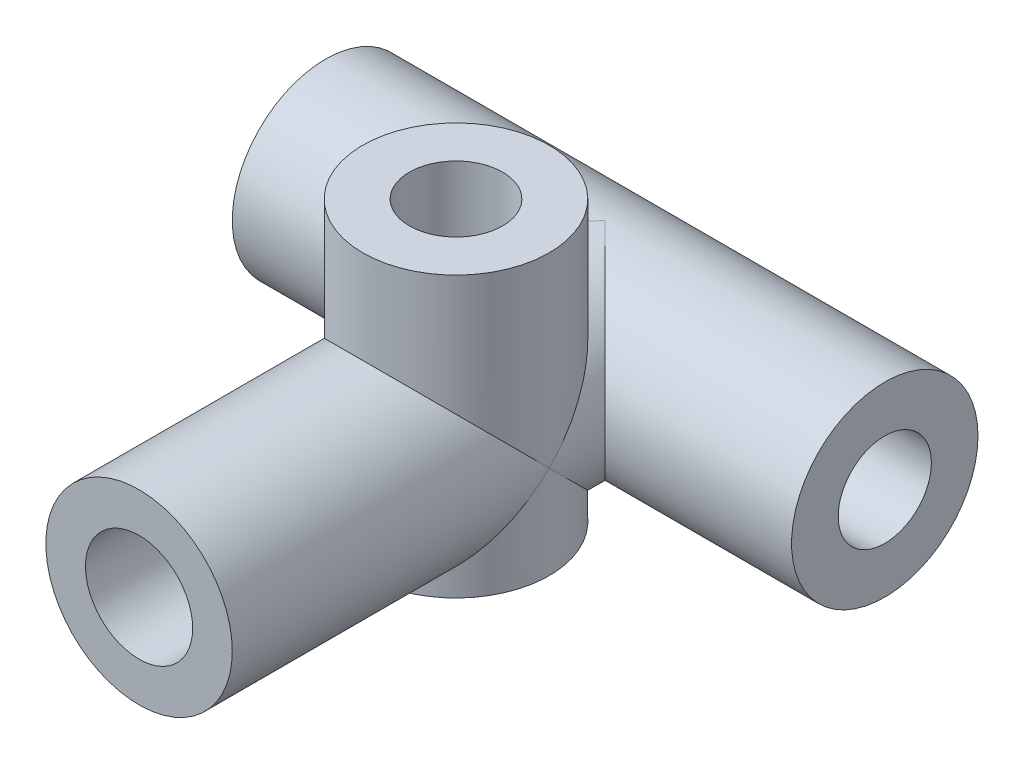
SolidWorks part; units mm, degrees
ref_plane "Plan de face" through (0, 0, 0) normal (0, 0, 1) x (1, 0, 0)
ref_plane "Plan de dessus" through (0, 0, 0) normal (0, 1, 0) x (1, 0, 0)
ref_plane "Plan de droite" through (0, 0, 0) normal (1, 0, 0) x (0, 0, -1)
sketch "Esquisse1" plane through (0, 0, 0) normal (1, 0, 0) x (0, 0, -1)
  circle A0 centre (0, 0) radius 2
  dimension "D1" = 4
extrude "Boss.-Extru.1" add sketch "Esquisse1" against normal blind 12
sketch "Esquisse5" plane through (0, 0, 0) normal (0, 0, 1) x (1, 0, 0)
  line L0 (-6, 2) -> (-6, -2) construction
  line L1 (0, 2) -> (-12, 2) construction
  line L2 (-12, -2) -> (0, -2) construction
  circle A0 centre (-6, 0) radius 2
extrude "Boss.-Extru.4" add sketch "Esquisse5" along normal blind 10 contours A0
sketch "Esquisse2" plane through (0, 0, 0) normal (1, 0, 0) x (0, 0, -1)
  circle A0 centre (0, 0) radius 1
  dimension "D1" = 2
extrude "Enlèv. mat.-Extru.1" cut sketch "Esquisse2" against normal through all
sketch "Esquisse7" plane through (0, 0, 0) normal (0, 1, 0) x (1, 0, 0)
  line L0 (-8, -3.2) -> (-4, -3.2) construction
  line L1 (-8, -2) -> (-8, -10) construction
  line L2 (-4, -10) -> (-4, -2) construction
  line L5 (-12, -2) -> (-8, -2) construction
  circle A0 centre (-6, -3.2) radius 2
  dimension "D2" = 4
  dimension "D1" = 1.2
extrude "Boss.-Extru.5" add sketch "Esquisse7" along normal blind 4 and the other way blind 2 contours A0
sketch "Esquisse8" plane through (0, 0, 10) normal (0, 0, 1) x (1, 0, 0)
  line L0 (-8, 0) -> (-4, 0) construction
  arc A0 (-6, 2) -> (-6, -2) centre (-6, 0) ccw construction
  circle A1 centre (-6, 0) radius 2 construction
  circle A2 centre (-6, 0) radius 1.15
  dimension "D1" = 2.3
extrude "Enlèv. mat.-Extru.3" cut sketch "Esquisse8" against normal up to surface (5.1637 mm away) contours A2 up to face at (-6, 4, 5.2)
sketch "Esquisse9" plane through (0, 4, 0) normal (0, 1, 0) x (1, 0, 0)
  line L0 (-8, -3.2) -> (-4, -3.2) construction
  circle A0 centre (-6, -3.2) radius 2 construction
  circle A1 centre (-6, -3.2) radius 2 construction
  circle A2 centre (-6, -3.2) radius 1
  dimension "D1" = 2
extrude "Enlèv. mat.-Extru.4" cut sketch "Esquisse9" against normal through all contours A2
chamfer "Chanfrein1" distance 0.4 angle 40 1 edges at (-6, -2, 4.2) first distance on face at (-6, -2, 4.2)
equation "\"e\"= 4"
equation "\"i\"= 1"
